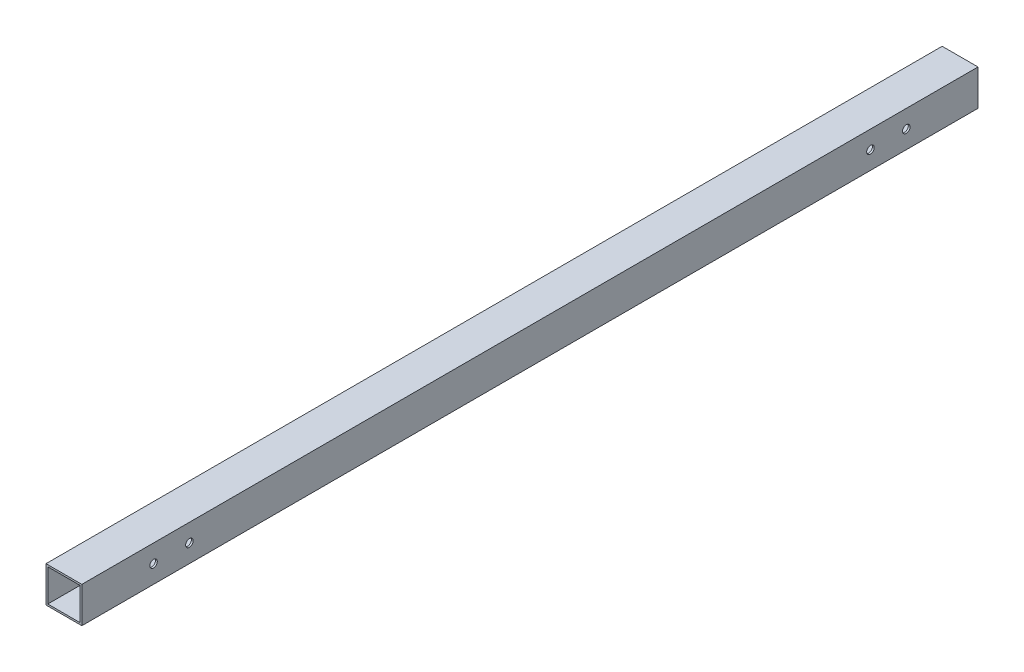
SolidWorks part; units mm, degrees
material "6061 合金"
ref_plane "前视基准面" through (0, 0, 0) normal (0, 0, 1) x (1, 0, 0)
ref_plane "上视基准面" through (0, 0, 0) normal (0, 1, 0) x (1, 0, 0)
ref_plane "右视基准面" through (0, 0, 0) normal (1, 0, 0) x (0, 0, -1)
other "Configuration Table"
sketch "草图1" plane through (0, 0, 0) normal (0, 0, 1) x (1, 0, 0)
  line L1 (0, 0) -> (20, 0)
  line L2 (0, 0) -> (0, -20)
  line L3 (0, -20) -> (20, -20)
  line L4 (20, 0) -> (20, -20)
  dimension "D1" = 20
extrude "拉伸-薄壁1" add sketch "草图1" along normal blind 500 thin thin type one direction reverse wall 1
sketch "草图2" plane through (20, 0, 0) normal (1, 0, 0) x (0, 0, -1)
  line L0 (-500, -20) -> (-500, 0) construction
  line L1 (-500, 0) -> (0, 0) construction
  line L2 (-250, 0) -> (-250, -150.9512) construction
  circle A0 centre (-460, -10) radius 2.1
  circle A1 centre (-440, -10) radius 2.1
  circle A2 centre (-60, -10) radius 2.1
  circle A3 centre (-40, -10) radius 2.1
  dimension "D1" = 4.2
  dimension "D2" = 40
  dimension "D3" = 10
  dimension "D5" = 20
  dimension "D4" = 2
extrude "切除-拉伸1" cut sketch "草图2" against normal blind 45
